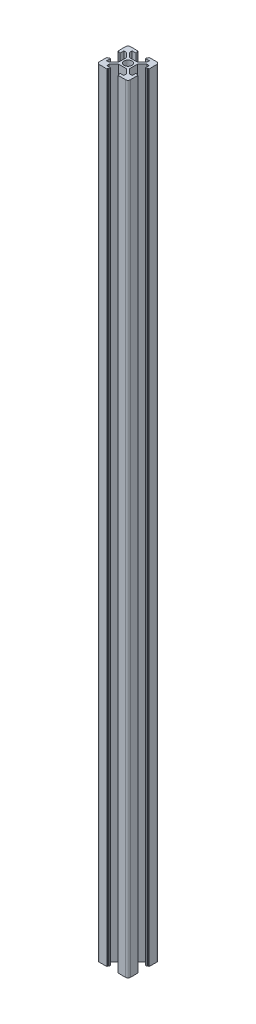
SolidWorks part; units mm, degrees
ref_plane "前视基准面" through (0, 0, 0) normal (0, 0, 1) x (1, 0, 0)
ref_plane "上视基准面" through (0, 0, 0) normal (0, 1, 0) x (1, 0, 0)
ref_plane "右视基准面" through (0, 0, 0) normal (1, 0, 0) x (0, 0, -1)
other "Configuration Table"
sketch "草图1" plane through (0, 0, 0) normal (0, 1, 0) x (1, 0, 0)
  line L0 (-5.8258, 3.4539) -> (-5.8258, 6.5539) construction
  line L1 (-5.8258, 5.9932) -> (-5.8258, 0.9145)
  line L2 (0.3135, 7.0539) -> (-4.7652, 7.0539)
  line L3 (1.3742, 0.9145) -> (1.3742, 5.9932)
  line L4 (-4.7652, -0.1461) -> (0.3135, -0.1461)
  line L5 (-12.2258, 3.4539) -> (7.7742, 3.4539) construction
  line L6 (-2.2258, 13.4539) -> (-2.2258, -6.5461) construction
  line L7 (-12.2258, 13.4539) -> (-2.2258, 3.4539) construction
  line L8 (-12.2258, 7.0539) -> (-5.8258, 7.0539) construction
  line L9 (-11.4258, 6.5539) -> (-5.3258, 6.5539) construction
  line L10 (-10.4258, 8.9539) -> (-7.7258, 8.9539) construction
  line L11 (-8.7865, 8.9539) -> (-5.8258, 5.9932) construction
  line L12 (-12.2258, 11.9539) -> (-12.2258, 7.0539)
  line L13 (-12.2258, 7.0539) -> (-11.4258, 7.0539)
  line L14 (-11.4258, 7.0539) -> (-11.4258, 6.5539)
  line L15 (-11.4258, 6.5539) -> (-10.4258, 6.5539)
  line L16 (-10.4258, 6.5539) -> (-10.4258, 8.9539)
  line L17 (-10.4258, 8.9539) -> (-8.7865, 8.9539)
  line L18 (-8.7865, 8.9539) -> (-5.8258, 5.9932)
  line L19 (-5.3258, 12.6539) -> (-5.3258, 11.6539)
  line L20 (-5.8258, 12.6539) -> (-5.3258, 12.6539)
  line L21 (-5.8258, 13.4539) -> (-5.8258, 12.6539)
  line L22 (-10.7258, 13.4539) -> (-5.8258, 13.4539)
  line L23 (-5.3258, 11.6539) -> (-7.7258, 11.6539)
  line L24 (-7.7258, 11.6539) -> (-7.7258, 10.0145)
  line L25 (-7.7258, 10.0145) -> (-4.7652, 7.0539)
  line L26 (7.7742, 13.4539) -> (-2.2258, 3.4539) construction
  line L27 (3.2742, 10.0145) -> (0.3135, 7.0539)
  line L28 (3.2742, 11.6539) -> (3.2742, 10.0145)
  line L29 (0.8742, 11.6539) -> (3.2742, 11.6539)
  line L30 (0.8742, 12.6539) -> (0.8742, 11.6539)
  line L31 (1.3742, 12.6539) -> (0.8742, 12.6539)
  line L32 (1.3742, 13.4539) -> (1.3742, 12.6539)
  line L33 (6.2742, 13.4539) -> (1.3742, 13.4539)
  line L34 (7.7742, 11.9539) -> (7.7742, 7.0539)
  line L35 (7.7742, 7.0539) -> (6.9742, 7.0539)
  line L36 (6.9742, 7.0539) -> (6.9742, 6.5539)
  line L37 (6.9742, 6.5539) -> (5.9742, 6.5539)
  line L38 (5.9742, 6.5539) -> (5.9742, 8.9539)
  line L39 (5.9742, 8.9539) -> (4.3348, 8.9539)
  line L40 (4.3348, 8.9539) -> (1.3742, 5.9932)
  line L41 (7.7742, -6.5461) -> (-2.2258, 3.4539) construction
  line L42 (4.3348, -2.0461) -> (1.3742, 0.9145)
  line L43 (5.9742, -2.0461) -> (4.3348, -2.0461)
  line L44 (5.9742, 0.3539) -> (5.9742, -2.0461)
  line L45 (6.9742, 0.3539) -> (5.9742, 0.3539)
  line L46 (6.9742, -0.1461) -> (6.9742, 0.3539)
  line L47 (7.7742, -0.1461) -> (6.9742, -0.1461)
  line L48 (7.7742, -5.0461) -> (7.7742, -0.1461)
  line L49 (6.2742, -6.5461) -> (1.3742, -6.5461)
  line L50 (1.3742, -6.5461) -> (1.3742, -5.7461)
  line L51 (1.3742, -5.7461) -> (0.8742, -5.7461)
  line L52 (0.8742, -5.7461) -> (0.8742, -4.7461)
  line L53 (0.8742, -4.7461) -> (3.2742, -4.7461)
  line L54 (3.2742, -4.7461) -> (3.2742, -3.1068)
  line L55 (3.2742, -3.1068) -> (0.3135, -0.1461)
  line L56 (-12.2258, -6.5461) -> (-2.2258, 3.4539) construction
  line L57 (-7.7258, -3.1068) -> (-4.7652, -0.1461)
  line L58 (-7.7258, -4.7461) -> (-7.7258, -3.1068)
  line L59 (-5.3258, -4.7461) -> (-7.7258, -4.7461)
  line L60 (-5.3258, -5.7461) -> (-5.3258, -4.7461)
  line L61 (-5.8258, -5.7461) -> (-5.3258, -5.7461)
  line L62 (-5.8258, -6.5461) -> (-5.8258, -5.7461)
  line L63 (-10.7258, -6.5461) -> (-5.8258, -6.5461)
  line L64 (-12.2258, -5.0461) -> (-12.2258, -0.1461)
  line L65 (-12.2258, -0.1461) -> (-11.4258, -0.1461)
  line L66 (-11.4258, -0.1461) -> (-11.4258, 0.3539)
  line L67 (-11.4258, 0.3539) -> (-10.4258, 0.3539)
  line L68 (-10.4258, 0.3539) -> (-10.4258, -2.0461)
  line L69 (-10.4258, -2.0461) -> (-8.7865, -2.0461)
  line L70 (-8.7865, -2.0461) -> (-5.8258, 0.9145)
  arc A0 (-12.2258, 11.9539) -> (-10.7258, 13.4539) centre (-10.7258, 11.9539) cw
  circle A1 centre (-2.2258, 3.4539) radius 2.5
  arc A2 (6.2742, 13.4539) -> (7.7742, 11.9539) centre (6.2742, 11.9539) cw
  arc A3 (7.7742, -5.0461) -> (6.2742, -6.5461) centre (6.2742, -5.0461) cw
  arc A4 (-10.7258, -6.5461) -> (-12.2258, -5.0461) centre (-10.7258, -5.0461) cw
  point P13 (-2.2258, 3.4539)
  point P84 (-2.2258, 3.4539)
  dimension "D8" = 1.5
  dimension "D9" = 5
  dimension "D1" = 20
  dimension "D2" = 6.2
  dimension "D3" = 7.2
  dimension "D4" = 11
  dimension "D5" = 1.5
  dimension "D6" = 0.8
  dimension "D7" = 1.8
  dimension "D10" = 7.2
extrude "凸台-拉伸1" add sketch "草图1" along normal blind 500
sketch "草图2" plane through (0, 0, -7.0539) normal (0, 0, -1) x (-1, 0, 0)
  line L0 (2.2258, 600) -> (2.2258, -49400) construction
  line L1 (-0.3135, 500) -> (4.7652, 500) construction
  line L2 (-0.3135, 0) -> (4.7652, 0) construction
  line L3 (-117.7742, 140) -> (-117.7742, 50140) construction
  line L4 (-317.7742, 140) -> (82.2258, 140) construction
  line L5 (-317.7742, 361.5) -> (82.2258, 361.5) construction
  line L9 (-6.2742, 0) -> (-1.3742, 0) construction
  line L10 (12.2258, 250) -> (-49987.7742, 250) construction
  line L11 (12.2258, 500) -> (12.2258, 0) construction
  line L12 (-246.2742, 500) -> (-246.2742, 0) construction
  circle A1 centre (2.2258, 130) radius 1.75
  circle A2 centre (2.2258, 370) radius 1.75
  point P4 (2.2258, 500)
  point P7 (2.2258, 0)
  point P12 (-117.7742, 140)
  point P15 (-117.7742, 361.5)
  point P24 (12.2258, 250)
  point P27 (-246.2742, 250)
  dimension "D1" = 3.5
  dimension "D2" = 130
extrude "切除-拉伸1" cut sketch "草图2" against normal blind 21
